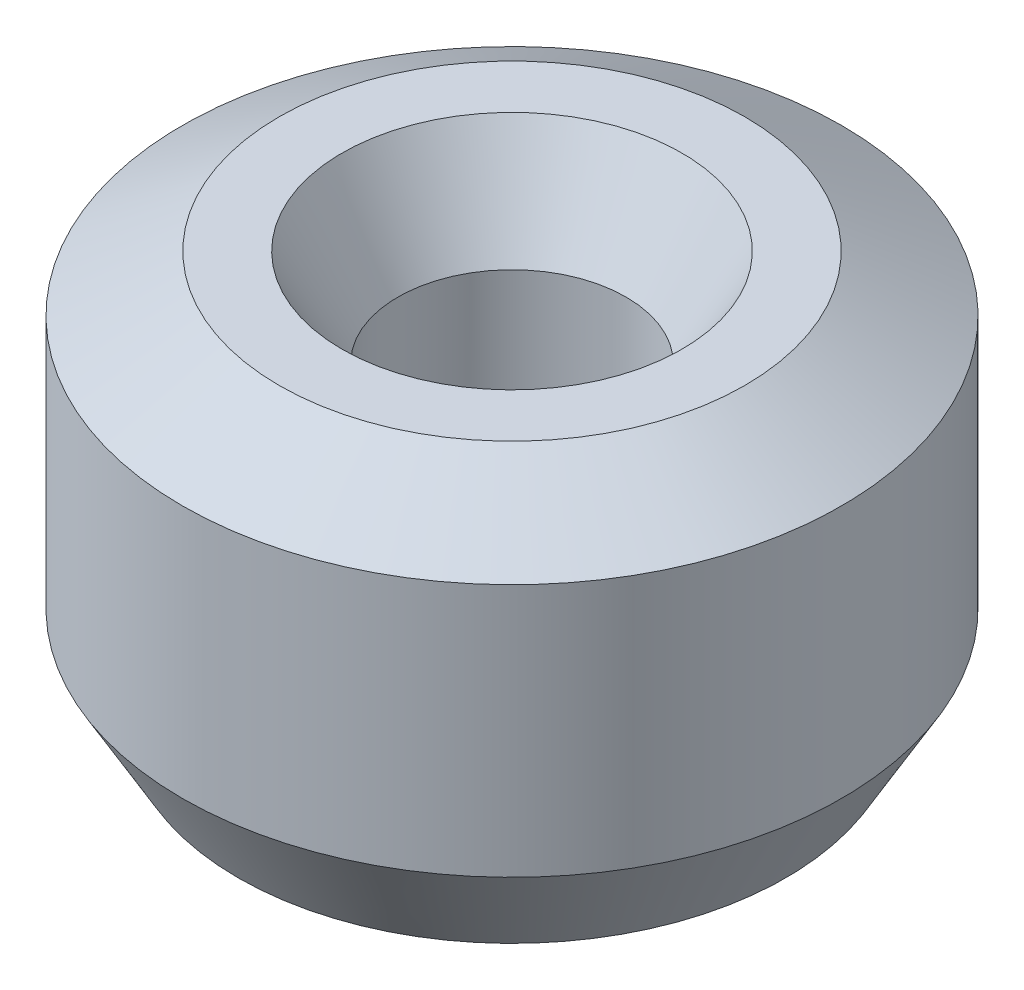
SolidWorks part; units mm, degrees
ref_plane "Front Plane" through (0, 0, 0) normal (0, 0, 1) x (1, 0, 0)
ref_plane "Top Plane" through (0, 0, 0) normal (0, 1, 0) x (1, 0, 0)
ref_plane "Right Plane" through (0, 0, 0) normal (1, 0, 0) x (0, 0, -1)
sketch "Sketch1" plane through (0, 0, 0) normal (0, 1, 0) x (1, 0, 0)
  circle A0 centre (0, 0) radius 5
  dimension "SLEEVE_OD" = 10
extrude "Boss-Extrude1" add sketch "Sketch1" along normal blind 6.1603
sketch "Sketch2" plane through (0, 0, 0) normal (0, 1, 0) x (1, 0, 0)
  circle A0 centre (0, 0) radius 1.7309
  dimension "BORE_D" = 3.4618
extrude "Cut-Extrude1" cut sketch "Sketch2" along normal through all
chamfer "Chamfer1" distance 0.8477 angle 60 4 edges at (0, 6.1603, 1.7309) (0, 0, 1.7309) (0, 0, 5) (0, 6.1603, 5) first distance on face at (0, 6.1603, 1.7309) first distance on face at (0, 0, 1.7309) first distance on face at (0, 6.1603, 5)
